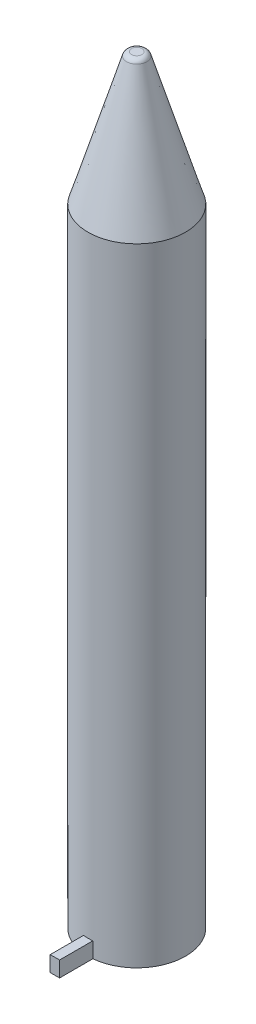
SolidWorks part; units mm, degrees
ref_plane "Front Plane" through (0, 0, 0) normal (0, 0, 1) x (1, 0, 0)
ref_plane "Top Plane" through (0, 0, 0) normal (0, 1, 0) x (1, 0, 0)
ref_plane "Right Plane" through (0, 0, 0) normal (1, 0, 0) x (0, 0, -1)
sketch "Sketch1" plane through (0, 0, 0) normal (0, 1, 0) x (1, 0, 0)
  circle A0 centre (0, 0) radius 9.398
  dimension "D1" = 18.796
extrude "Boss-Extrude1" add sketch "Sketch1" along normal blind 120.65
sketch "Sketch2" plane through (0, 0, 0) normal (0, 0, 1) x (1, 0, 0)
  line L8 (0, 120.65) -> (0, 146.05)
  line L9 (9.398, 120.65) -> (-9.398, 120.65) construction
  line L10 (1.9575, 145.3386) -> (9.398, 120.65)
  line L11 (9.398, 120.65) -> (0, 120.65)
  line L12 (1, 146.05) -> (0, 146.05)
  arc A3 (1, 146.05) -> (1.9575, 145.3386) centre (1, 145.05) cw
  dimension "D2" = 25.4
  dimension "D1" = 1
revolve "Revolve1" add sketch "Sketch2" angle 360 about L8
sketch "Sketch3" plane through (0, 0, 0) normal (0, -1, 0) x (1, 0, 0)
  line L1 (-0.9, 15.75) -> (0.9, 15.75)
  line L2 (-0.9, 15.75) -> (-0.9, 9.3548)
  line L4 (0.9, 15.75) -> (0.9, 9.3548)
  arc A0 (0.9, 9.3548) -> (-0.9, 9.3548) centre (0, 0) ccw
  dimension "D1" = 0.9
  dimension "D3" = 15.75
extrude "Boss-Extrude2" add sketch "Sketch3" against normal blind 3
sketch "Sketch4" plane through (0, 0, 0) normal (0, -1, 0) x (1, 0, 0)
  circle A0 centre (0, 0) radius 2.5
  dimension "D1" = 5
extrude "Cut-Extrude1" cut sketch "Sketch4" against normal blind 2.54
